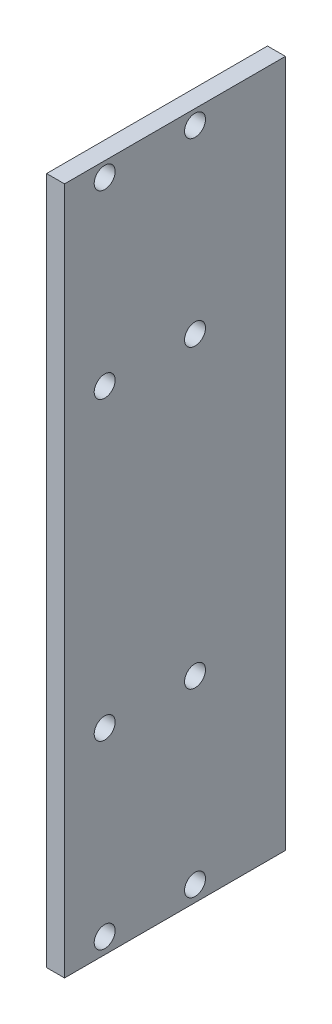
SolidWorks part; units mm, degrees
ref_plane "Front" through (0, 0, 0) normal (0, 0, 1) x (1, 0, 0)
ref_plane "Top" through (0, 0, 0) normal (0, 1, 0) x (1, 0, 0)
ref_plane "Right" through (0, 0, 0) normal (1, 0, 0) x (0, 0, -1)
ref_axis "side-side" through (80.9, 0, 0) along (-1, 0, 0)
ref_axis "up-down" through (0, 50, 0) along (0, -1, 0)
ref_axis "front-back" through (0, 0, -80.9) along (0, 0, 1)
sketch "Sketch1" plane through (0, 0, 0) normal (1, 0, 0) x (0, 0, -1)
  line L0 (-42.8868, -19) -> (-42.8868, 103) construction
  line L1 (-111.9504, -18.796) -> (-52.4128, -18.796) construction
  line L2 (-82, -18.796) -> (-42.8868, -18.796)
  line L3 (-82, -18.796) -> (-82, 103)
  line L4 (-82, 103) -> (-42.8868, 103)
  line L5 (-42.8868, -18.796) -> (-42.8868, 103)
  line L6 (0, 50) -> (0, -50) construction
  circle A0 centre (-74.8898, -16) radius 1.8542
  circle A1 centre (-58.8898, -16) radius 1.8542
  circle A2 centre (-74.8898, 16) radius 1.8542
  circle A3 centre (-58.8898, 16) radius 1.8542
  circle A4 centre (-74.8898, 100.4311) radius 1.8542
  circle A5 centre (-58.8898, 100.4311) radius 1.8542
  circle A6 centre (-74.8898, 68.4311) radius 1.8542
  circle A7 centre (-58.8898, 68.4311) radius 1.8542
  dimension "D2" = 3.7084
  dimension "D1" = 82
extrude "Boss-Extrude1" add sketch "Sketch1" along normal blind 3.175
